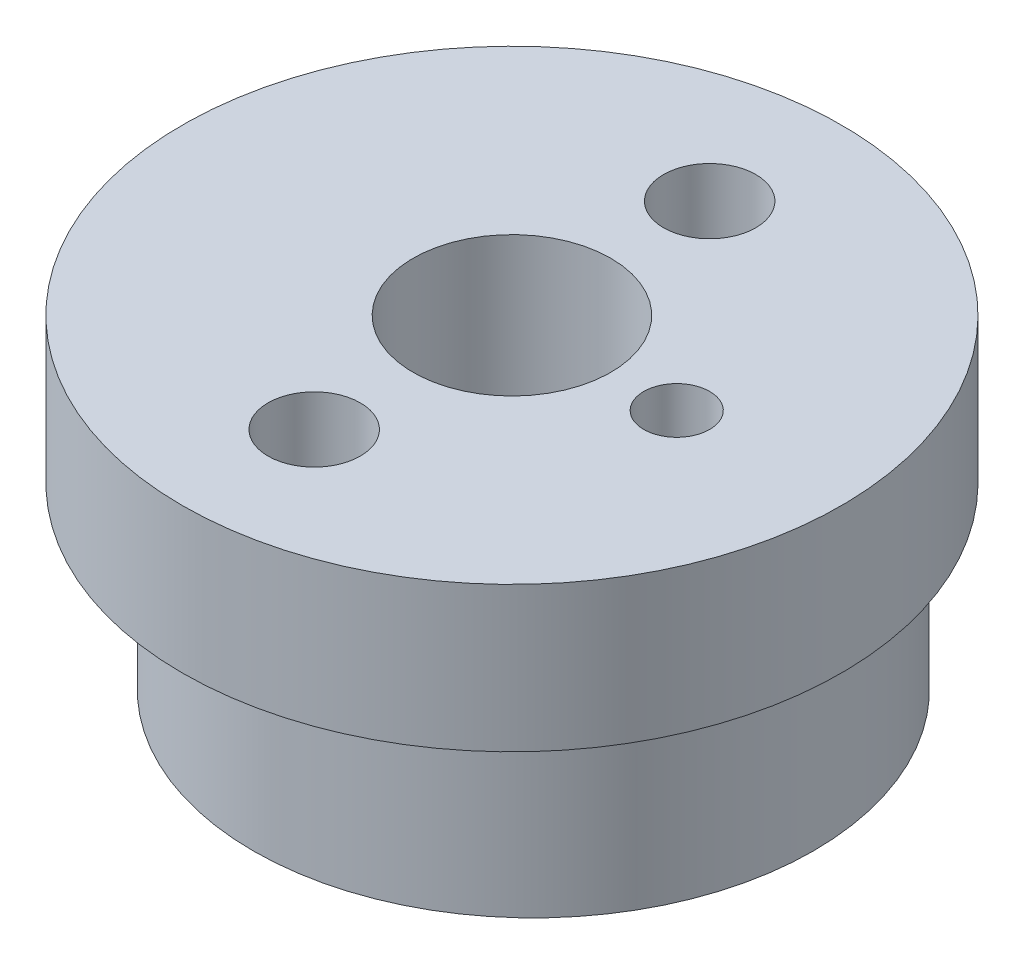
SolidWorks part; units mm, degrees
ref_plane "Front Plane" through (0, 0, 0) normal (0, 0, 1) x (1, 0, 0)
ref_plane "Top Plane" through (0, 0, 0) normal (0, 1, 0) x (1, 0, 0)
ref_plane "Right Plane" through (0, 0, 0) normal (1, 0, 0) x (0, 0, -1)
sketch "Sketch1" plane through (0, 0, 0) normal (0, 1, 0) x (1, 0, 0)
  circle A0 centre (0, 0) radius 8.5
  dimension "D1" = 17
extrude "Boss-Extrude1" add sketch "Sketch1" along normal blind 5.5
sketch "Sketch2" plane through (0, 5.5, 0) normal (0, 1, 0) x (1, 0, 0)
  circle A0 centre (-0.65, 0) radius 10
  dimension "D1" = 20
  dimension "D2" = 0.65
extrude "Boss-Extrude2" add sketch "Sketch2" along normal blind 4 and the other way blind 0.4
sketch "Sketch3" plane through (0, 0, 0) normal (0, -1, 0) x (1, 0, 0)
  circle A0 centre (-0.65, 0) radius 3
  circle A3 centre (-0.65, 0) radius 10 construction
  dimension "D1" = 6
extrude "Cut-Extrude1" cut sketch "Sketch3" against normal through all
sketch "Sketch6" plane through (0, 0, 0) normal (0, -1, 0) x (1, 0, 0)
  line L3 (4.35, 0) -> (0, 0) construction
  circle A0 centre (0, 0) radius 8.5 construction
  circle A2 centre (0, 0) radius 8.5 construction
  circle A4 centre (4.35, 0) radius 1
  dimension "D1" = 2
extrude "Cut-Extrude4" cut sketch "Sketch6" against normal through all contours A4
hole_wizard "Ø2.8 (2.8) Diameter Hole1" positions "Sketch7" profile "Sketch8" hole size "Ø2.8" standard "DIN" end condition up to next
sketch "Sketch7" plane through (0, 0, 0) normal (0, -1, 0) x (-1, 0, 0)
  line L0 (0.65, -6) -> (0.65, 0)
  line L1 (0.65, 0) -> (0.65, 6)
  circle A0 centre (0.65, 0) radius 6
  circle A1 centre (0.65, 0) radius 3 construction
  point P0 (0.65, 6)
  point P2 (0.65, -6)
  dimension "D1" = 12
sketch "Sketch8" plane through (-0.65, 0, -6) normal (1, 0, 0) x (0, 0, -1)
  line L0 (0, 0) -> (0, 9.5)
  line L1 (0, 9.5) -> (1.4, 9.5)
  line L2 (1.4, 9.5) -> (1.4, 0)
  line L5 (1.4, 0) -> (0, 0)
  line L11 (0, -6.35) -> (0, 107.95) construction
  dimension "Thru Hole Dia." = 2.8
  dimension "Thru Hole Depth" = 9.5
